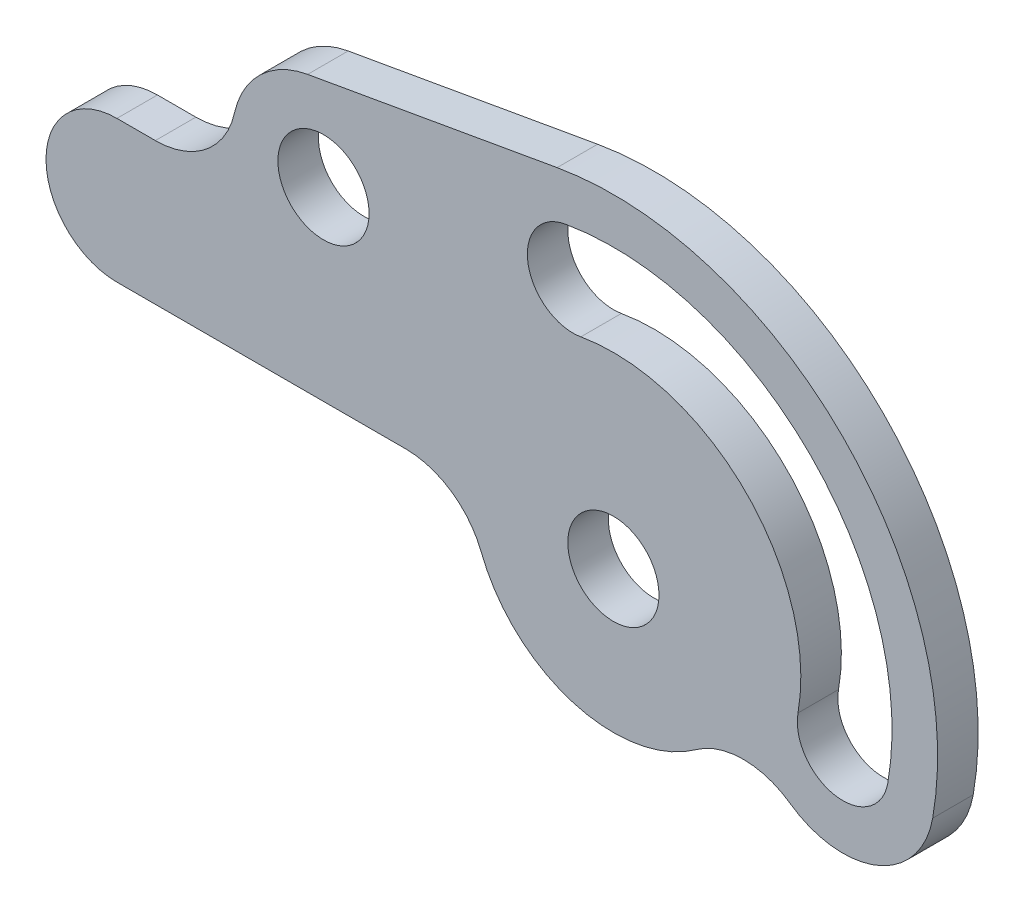
SolidWorks part; units mm, degrees
ref_plane "Front Plane" through (0, 0, 0) normal (0, 0, 1) x (1, 0, 0)
ref_plane "Top Plane" through (0, 0, 0) normal (0, 1, 0) x (1, 0, 0)
ref_plane "Right Plane" through (0, 0, 0) normal (1, 0, 0) x (0, 0, -1)
sketch "Sketch1" plane through (0, 0, 0) normal (0, 0, 1) x (1, 0, 0)
  line L0 (0, 0) -> (9.1281, 0) construction
  line L1 (0, 0) -> (0, 9.1281) construction
  line L2 (0, 0) -> (12.5071, -2.2053) construction
  line L3 (0, 0) -> (-2.2053, 12.5071) construction
  line L4 (-1.5851, 8.9894) -> (-11.3562, 7.2665) construction
  line L5 (0, 5.5562) -> (-22.225, 5.5562) construction
  line L6 (0, 0) -> (-22.225, 0) construction
  line L7 (-22.225, 0) -> (-22.225, 5.5562) construction
  line L8 (-19.4469, 5.5562) -> (-14.492, 5.5562)
  line L9 (-19.4469, 0) -> (-5.5562, 0)
  line L10 (-10.736, 3.7489) -> (-11.9765, 10.7841) construction
  line L11 (-11.9765, 10.7841) -> (-2.2053, 12.5071)
  circle A0 centre (0, 0) radius 1.7859
  circle A1 centre (0, 0) radius 5.5562
  circle A2 centre (0, 0) radius 9.1281 construction
  circle A3 centre (-1.5851, 8.9894) radius 1.7859
  circle A4 centre (8.9894, -1.5851) radius 1.7859
  circle A5 centre (-11.3562, 7.2665) radius 1.7859
  circle A6 centre (8.9894, -1.5851) radius 3.5719
  circle A7 centre (-1.5851, 8.9894) radius 3.5719
  circle A8 centre (-11.3562, 7.2665) radius 3.5719
  circle A9 centre (-19.4469, 2.7781) radius 2.7781
  arc A10 (7.2306, -1.275) -> (-1.275, 7.2306) centre (0, 0) ccw
  arc A11 (10.7483, -1.8952) -> (-1.8952, 10.7483) centre (0, 0) ccw
  arc A12 (12.5071, -2.2053) -> (-2.2053, 12.5071) centre (0, 0) ccw
  point P24 (-22.225, 2.7781)
  point P35 (-11.3562, 7.2665)
  point P36 (-9.5974, 7.5767)
  point P37 (-3.3439, 8.6793)
  dimension "D4" = 7.1437
  dimension "D5" = 11.1125
  dimension "D6" = 3.5719
  dimension "D1" = 6.35
  dimension "D2" = 10
  dimension "D3" = 10
  dimension "D7" = 22.225
extrude "Boss-Extrude1" add sketch "Sketch1" along normal blind 1.5875 contours A9 | A9 L9 A1 A7 L11 A8 L8 | A8 A5 | A1 A0 | A11 A4 A10 A6 | A6 A10 A7 A1 | A11 A7 A10 A3 | A6 A12 A7 A11 region at (-16.9694, 5.3331, 0) region at (-19.4469, 2.7781, 0) region at (-14.4838, 8.7715, 0) region at (-4.1359, 3.4705, 0) region at (8.8312, 8.8312, 0) region at (-0.1357, 12.1469, 0) region at (4.2073, 4.2073, 0) region at (6.1384, 0.4003, 0)
fillet "Fillet1" radius 3.175 3 edges at (5.4718, -0.9648, 0.7937) (-5.5562, 0, 0.7937) (-14.492, 5.5562, 0.7937)
